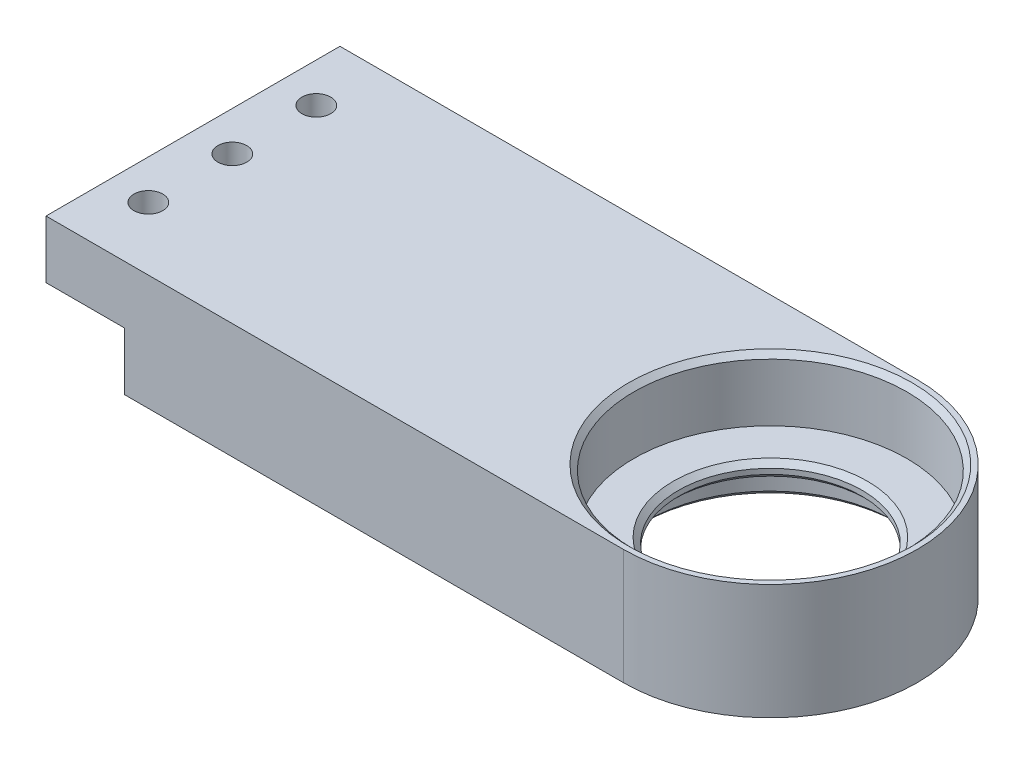
SolidWorks part; units mm, degrees
ref_plane "Front" through (0, 0, 0) normal (0, 0, 1) x (1, 0, 0)
ref_plane "Top" through (0, 0, 0) normal (0, 1, 0) x (1, 0, 0)
ref_plane "Right" through (0, 0, 0) normal (1, 0, 0) x (0, 0, -1)
sketch "草图1" plane through (0, 0, 0) normal (0, 1, 0) x (1, 0, 0)
  line L0 (-128.7916, 0) -> (62.2219, 0) construction
  line L1 (0, 56.2704) -> (0, -41.1981) construction
  line L3 (0, 28) -> (-110, 28)
  line L4 (0, 28) -> (0, -28) construction
  line L5 (0, -28) -> (-110, -28)
  line L6 (-110, 28) -> (-110, -28)
  arc A0 (0, 28) -> (0, -28) centre (0, 0) cw
  dimension "D1" = 110
  dimension "D2" = 28
  dimension "D3" = 56
extrude "凸台-拉伸1" add sketch "草图1" along normal blind 22
sketch "草图2" plane through (0, 0, 28) normal (0, 0, 1) x (1, 0, 0)
  line L1 (-110, 0) -> (-95, 0)
  line L2 (-110, 0) -> (-110, 11)
  line L3 (-110, 11) -> (-95, 11)
  line L4 (-95, 0) -> (-95, 11)
  dimension "D1" = 11
  dimension "D2" = 15
extrude "切除-拉伸1" cut sketch "草图2" against normal up to next
sketch "草图3" plane through (0, 22, 0) normal (0, 1, 0) x (1, 0, 0)
  circle A0 centre (0, 0) radius 26
  dimension "D1" = 52
extrude "切除-拉伸2" cut sketch "草图3" against normal blind 12
sketch "草图4" plane through (0, 10, 0) normal (0, 1, 0) x (1, 0, 0)
  circle A0 centre (0, 0) radius 17.5
  dimension "D1" = 35
extrude "切除-拉伸3" cut sketch "草图4" against normal up to next
sketch "草图5" plane through (0, 0, 0) normal (0, -1, 0) x (1, 0, 0)
  circle A0 centre (0, 0) radius 23.5
  dimension "D1" = 47
extrude "切除-拉伸4" cut sketch "草图5" against normal blind 7
chamfer "倒角1" distance 1 angle 45 4 edges at (0, 22, 26) (0, 0, -23.5) (0, 7, -17.5) (0, 10, 17.5)
sketch "草图6" plane through (0, 22, 0) normal (0, 1, 0) x (1, 0, 0)
  line L0 (-102.5, 37.393) -> (-102.5, -44.722) construction
  line L1 (-118.8522, 0) -> (50.1642, 0) construction
  line L2 (-110, 28) -> (-110, -28) construction
  circle A0 centre (-102.5, 0) radius 2.75
  circle A1 centre (-102.5, 16) radius 2.75
  circle A2 centre (-102.5, -16) radius 2.75
  point P7 (-102.5, 0)
  dimension "D2" = 5.5
  dimension "D3" = 5.5
  dimension "D1" = 7.5
  dimension "D4" = 16
extrude "切除-拉伸5" cut sketch "草图6" against normal up to next
sketch "草图7" plane through (0, 0, 28) normal (0, 0, 1) x (1, 0, 0)
  line L0 (-110, 22) -> (0, 22) construction
  line L1 (-40, 22) -> (28, 22)
  line L2 (-40, 22) -> (-40, 15) construction
  line L3 (-40, 15) -> (28, 15)
  line L4 (28, 22) -> (28, 15)
  line L5 (28, 0) -> (28, 22) construction
  line L6 (0, 22) -> (0, 0) construction
  line L7 (-40, 15) -> (-56.7697, 22)
  line L8 (-56.7697, 22) -> (-40, 22)
  dimension "D1" = 7
  dimension "D2" = 40
extrude "切除-拉伸6" [suppressed] cut sketch "草图7" against normal up to next
